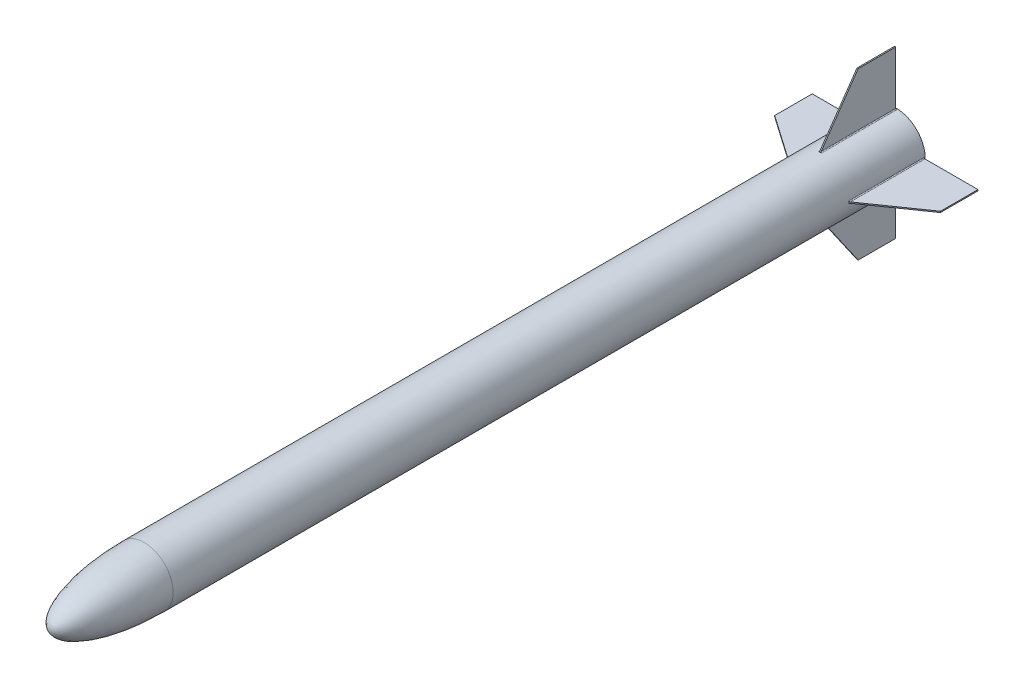
SolidWorks part; units mm, degrees
ref_plane "Front Plane" through (0, 0, 0) normal (0, 0, 1) x (1, 0, 0)
ref_plane "Top Plane" through (0, 0, 0) normal (0, 1, 0) x (1, 0, 0)
ref_plane "Right Plane" through (0, 0, 0) normal (1, 0, 0) x (0, 0, -1)
sketch "Sketch2" plane through (0, 0, 0) normal (1, 0, 0) x (0, 0, -1)
  line L0 (254, 78.3229) -> (2289.4925, 78.3229)
  line L1 (2289.4925, 78.3229) -> (2289.4925, 0)
  line L2 (2289.4925, 0) -> (0, 0)
  line L3 (0, 0) -> (-254, 0) construction
  line L4 (0, 0) -> (2.1037, 78.3229) construction
  ellipse E0 centre (254, 0) end of major axis (0, 0) minor radius 78.3229 (254, 78.3229) -> (0, 0) ccw
  point P1 (156.718, 78.3229)
  point P14 (133.0677, 0)
  point P15 (123.166, 0)
  point P16 (0, 0)
  point P17 (108.5128, 0)
  point P18 (0, 0)
  point P19 (156.718, -78.3229)
  dimension "D1" = 2035.4925
  dimension "D2" = 254
  dimension "D3" = 78.3229
  dimension "D5" = 254
  dimension "D4" = 78.3229
revolve "Revolve1" add sketch "Sketch2" angle 360 about L2
sketch "Sketch3" plane through (0, 0, -2289.4925) normal (0, 0, -1) x (-1, 0, 0)
  circle A0 centre (0, 0) radius 43.942
  dimension "D1" = 87.884
extrude "Boss-Extrude1" add sketch "Sketch3" along normal blind 15.24
ref_plane "Plane1" through (0, 254, 0) normal (0, 1, 0) x (1, 0, 0)
sketch "Sketch4" plane through (0, 254, 0) normal (0, 1, 0) x (1, 0, 0)
  line L1 (-1.5875, 2083.1175) -> (1.5875, 2083.1175)
  line L2 (-1.5875, 2083.1175) -> (-1.5875, 2286.3175)
  line L3 (-1.5875, 2286.3175) -> (1.5875, 2286.3175)
  line L4 (1.5875, 2083.1175) -> (1.5875, 2286.3175)
  line L5 (78.3229, 2289.4925) -> (-78.3229, 2289.4925) construction
  point P6 (0, 2286.3175)
  dimension "D1" = 3.175
  dimension "D2" = 3.175
  dimension "D3" = 203.2
extrude "Boss-Extrude2" add sketch "Sketch4" against normal up to surface (175.6932 mm away) up to face at (-78.3229, 0, -254)
sketch "Sketch5" plane through (-1.5875, 0, 0) normal (-1, 0, 0) x (0, 0, 1)
  line L0 (-2286.3175, 224.3568) -> (-2184.7175, 224.3568)
  line L1 (-2286.3175, 78.3068) -> (-2286.3175, 254) construction
  line L2 (-2184.7175, 224.3568) -> (-2083.1175, 78.3068)
  line L3 (-2083.1175, 78.3068) -> (-2083.1175, 254)
  line L4 (-2083.1175, 254) -> (-2286.3175, 254)
  line L5 (-2286.3175, 254) -> (-2286.3175, 224.3568)
  dimension "D1" = 101.6
  dimension "D2" = 146.05
extrude "Cut-Extrude1" cut sketch "Sketch5" against normal up to next
fillet "Fillet1" radius 2.54 2 edges at (1.5875, 78.3068, -2184.7175) (-1.5875, 78.3068, -2184.7175)
pattern_circular "CirPattern1" count 4 over 360 about axis through (0, 0, -2289.4925) along (0, 0, -1) of "Cut-Extrude1", "Fillet1", "Boss-Extrude2"
equation "\"Body Tube Length\"= 80.1375"
equation "\"D1@Sketch2\"=\"Body Tube Length\""
equation "\"Retainer Diameter\"= 3.46"
equation "\"D1@Sketch3\"=\"Retainer Diameter\""
equation "\"Retainer Height\"= 0.6"
equation "\"D1@Boss-Extrude1\"=\"Retainer Height\""
equation "\"Fin Offset\"= .125"
equation "\"D1@Sketch4\"=\"Fin Offset\""
equation "\"Fin Thickness\"= .125"
equation "\"D2@Sketch4\"=\"Fin Thickness\""
equation "\"Fin Root Chord\"= 8"
equation "\"D3@Sketch4\"=\"Fin Root Chord\""
equation "\"Fin Tip Chord\"= 4"
equation "\"D1@Sketch5\"=\"Fin Tip Chord\""
equation "\"Fin Height\"= 5.75"
equation "\"D2@Sketch5\"=\"Fin Height\""
equation "\"Fin Epoxy Fillet Radius\"=0.1"
equation "\"D1@Fillet1\"=\"Fin Epoxy Fillet Radius\""
equation "\"Nosecone Length\" = 10"
equation "\"D2@Sketch2\"=\"Nosecone Length\""
equation "\"Rocket Radius\"=3.08358"
equation "\"D3@Sketch2\"= \"Rocket Radius\""
equation "\"D5@Sketch2\"=\"Nosecone Length\""
equation "\"D4@Sketch2\"=\"Rocket Radius\""
